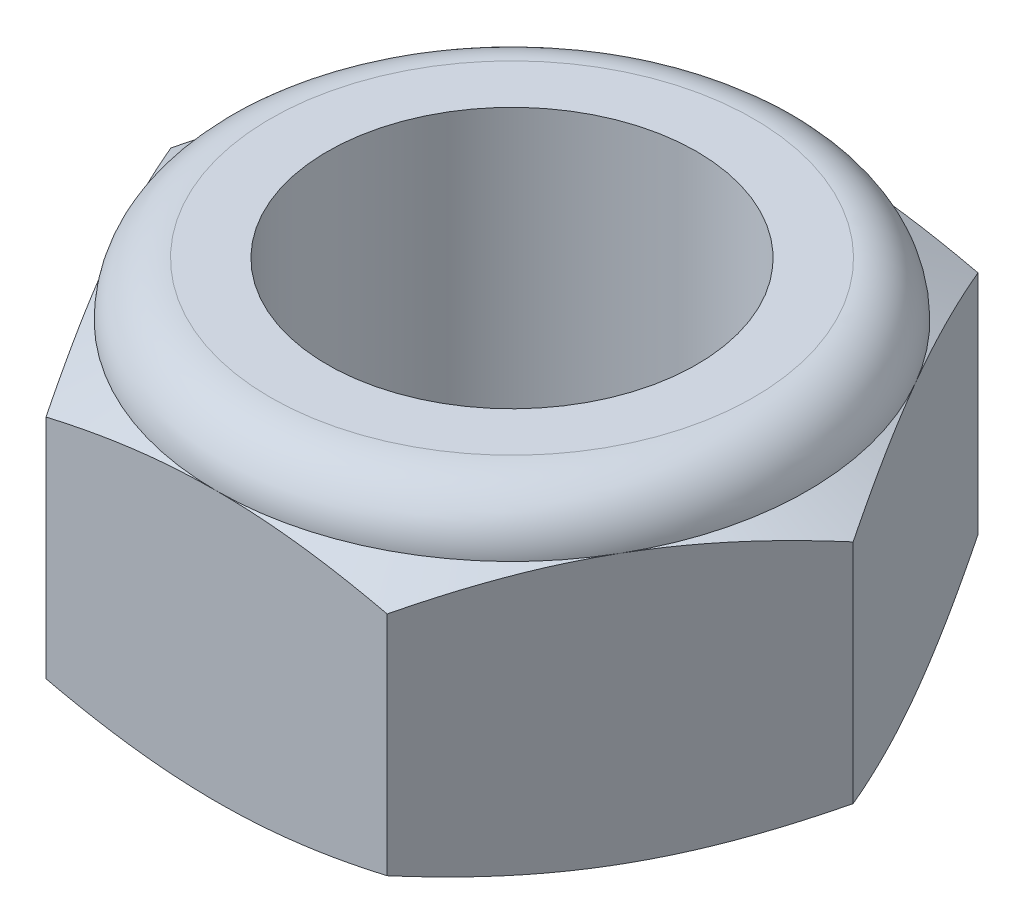
SolidWorks part; units mm, degrees
material "Steel Fastener"
ref_plane "FRONT" through (0, 0, 0) normal (0, 0, 1) x (1, 0, 0)
ref_plane "TOP" through (0, 0, 0) normal (0, 1, 0) x (1, 0, 0)
ref_plane "RIGHT" through (0, 0, 0) normal (1, 0, 0) x (0, 0, -1)
sketch "Sketch1" plane through (0, 0, 0) normal (0, 1, 0) x (1, 0, 0)
  line L0 (58.6588, 0) -> (29.3294, 50.8)
  line L1 (29.3294, 50.8) -> (-29.3294, 50.8)
  line L2 (-29.3294, 50.8) -> (-58.6588, 0)
  line L3 (-58.6588, 0) -> (-29.3294, -50.8)
  line L4 (-29.3294, -50.8) -> (29.3294, -50.8)
  line L5 (29.3294, -50.8) -> (58.6588, 0)
  circle A0 centre (0, 0) radius 50.8 construction
  dimension "HEX_SIZE" = 101.6
  dimension "D1" = 120
extrude "Base-Extrude" add sketch "Sketch1" along normal blind 55.5752
sketch "Sketch2" plane through (0, 0, 0) normal (0, -1, 0) x (-1, 0, 0)
  circle A0 centre (0, 0) radius 31.75
  dimension "DIA" = 63.5
extrude "Cut-Extrude1" cut sketch "Sketch2" against normal through all
ref_plane "Plane2" [suppressed] through (0, -0.381, 0) normal (0, 1, 0) x (-1, 0, 0)
sketch "Sketch4" [suppressed] plane through (0, -0.381, 0) normal (0, 1, 0) x (-1, 0, 0)
  circle A0 centre (0, 0) radius 5.08
  circle A1 centre (0, 0) radius 1.778 construction
  circle A2 centre (0, 0) radius 1.778
  dimension "D1" = 10.16
extrude "WASHER" [suppressed] add sketch "Sketch4" along normal blind 0.381
sketch "Sketch5" [suppressed] plane through (0, -0.381, 0) normal (0, -1, 0) x (1, 0, 0)
  line L0 (-4.0579, -0.222) -> (-4.6765, -0.2558)
  line L1 (-3.9735, 0.8527) -> (-4.5793, 0.9827)
  line L2 (4.5402, 0) -> (-4.5402, 0) construction
  circle A0 centre (0, 0) radius 5.08 construction
  arc A1 (-3.9735, 0.8527) -> (-4.0579, -0.222) centre (0, 0) ccw
  arc A2 (-4.8641, 1.4651) -> (-5.0332, -0.6878) centre (0, 0) ccw
  arc A3 (-5.0332, -0.6878) -> (-4.6765, -0.2558) centre (-4.6557, -0.6362) cw
  arc A4 (-4.8641, 1.4651) -> (-4.5793, 0.9827) centre (-4.4993, 1.3552) ccw
  point P13 (-5.08, 0)
  dimension "D3" = 0.381
  dimension "D4" = 4.064
  dimension "D1" = 12.112
  dimension "D2" = 15.242
extrude "TOOTH" [suppressed] cut sketch "Sketch5" against normal up to surface (0.381 mm away)
pattern_circular "TOOTHPattern" [suppressed] count 12 every 30
sketch "Sketch6" plane through (0, 55.5752, 0) normal (0, 1, 0) x (-1, 0, 0)
  circle A0 centre (0, 0) radius 25.4
  dimension "D1" = 50.8
extrude "Cut-Extrude2" [suppressed] cut sketch "Sketch6" against normal blind 10.414 flip side to cut
sketch "Sketch7" plane through (0, 0, 0) normal (0, 0, 1) x (1, 0, 0)
  line L0 (58.6588, 8.382) -> (52.5628, 8.382)
  line L2 (58.6588, 55.5752) -> (58.6588, 0) construction
  line L3 (58.6588, 4.318) -> (58.6588, 8.382)
  line L5 (52.5628, 8.382) -> (58.6588, 4.318)
  line L6 (0, 18.8905) -> (0, 0) construction
  line L7 (0, 55.5752) -> (0, 0) construction
  dimension "D1" = 4.064
  dimension "D2" = 6.096
  dimension "D3" = 8.382
revolve "Cut-Revolve2" [suppressed] cut sketch "Sketch7" angle 360 about L6
fillet "Fillet1" [suppressed] radius 0.254
chamfer "Chamfer1" [suppressed] distance 0.762 angle 45
ref_axis "REF AXIS" [suppressed] through (0, 0, 43.7261) along (0, 0, -1)
ref_plane "REF BASE PLANE" [suppressed] through (0, 0, 0) normal (-0.5373, 0.8434, 0) x (0, 0, -1)
ref_plane "DOT PLANE" [suppressed] through (2.7295, -4.2844, 0) normal (0.5373, -0.8434, 0) x (0, 0, 1)
sketch "Sketch9" [suppressed] plane through (2.7295, -4.2844, 0) normal (0.5373, -0.8434, 0) x (0, 0, 1)
  line L0 (0, -13.5388) -> (0, -11.1515)
  line L1 (0, -5.9533) -> (0, -4.1474) construction
  line L2 (0, -22.7912) -> (0, 0) construction
  arc A0 (0, -13.5388) -> (0, -11.1515) centre (0, -12.3452) cw
revolve "Revolve1" [suppressed] add sketch "Sketch9" angle 360 about L1
pattern_circular "CirPattern1" [suppressed] count 6 over 360 of bodies 104
sketch "Sketch10" plane through (0, 0, 0) normal (0, 0, 1) x (1, 0, 0)
  line L0 (0, 0) -> (0, 57.4313) construction
  line L1 (0, 56.8452) -> (59.9186, 56.8452)
  line L2 (59.9186, 56.8452) -> (59.9186, -1.27)
  line L3 (59.9186, -1.27) -> (0, -1.27)
  line L4 (0, -1.27) -> (0, 0)
  line L5 (0, 0) -> (50.8102, 0)
  line L7 (41.529, 55.5752) -> (0, 55.5752)
  line L8 (0, 55.5752) -> (0, 56.8452)
  line L9 (50.8102, 0) -> (58.6588, 3.6599)
  line L10 (29.3294, 0) -> (58.6588, 0) construction
  line L11 (50.8, 46.3042) -> (58.6588, 42.6396)
  line L12 (29.3294, 55.5752) -> (58.6588, 55.5752) construction
  line L13 (58.6588, 55.5752) -> (58.6588, 0) construction
  line L14 (58.6588, 42.6396) -> (58.6588, 3.6599)
  line L15 (-58.6588, 55.5752) -> (-58.6588, 0) construction
  line L16 (-29.3294, 55.5752) -> (29.3294, 55.5752) construction
  arc A0 (50.8, 46.3042) -> (41.529, 55.5752) centre (41.529, 46.3042) ccw
  point P20 (59.9186, 27.7876)
  dimension "D1" = 1.27
  dimension "D2" = 1.27
  dimension "D3" = 1.2598
  dimension "D4" = 25
  dimension "D5" = 55.5752
  dimension "D7" = 41.529
  dimension "D8" = 9.271
  dimension "D9" = 25
  dimension "D10" = 7.8486
  dimension "D11" = 117.3176
revolve "Cut-Revolve3" cut sketch "Sketch10" angle 360 about axis through (0, 55.5752, 0) along (0, -1, 0)
